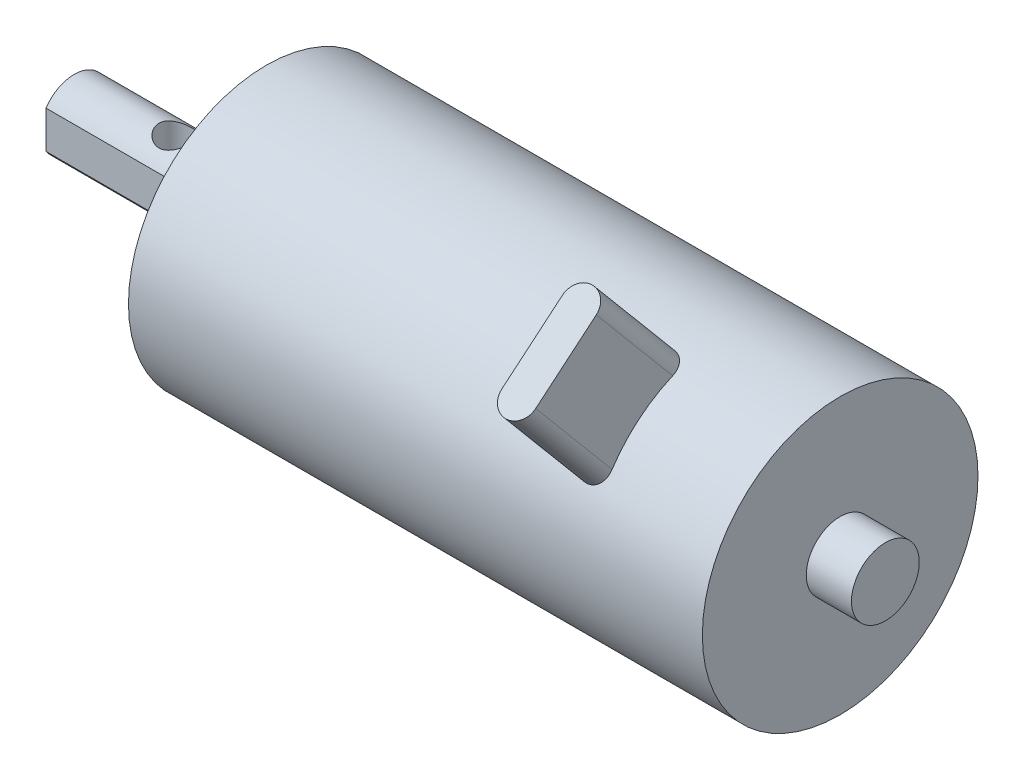
SolidWorks part; units mm, degrees
ref_plane "前视基准面" through (0, 0, 0) normal (0, 0, 1) x (1, 0, 0)
ref_plane "上视基准面" through (0, 0, 0) normal (0, 1, 0) x (1, 0, 0)
ref_plane "右视基准面" through (0, 0, 0) normal (1, 0, 0) x (0, 0, -1)
sketch "草图1" plane through (0, 0, 0) normal (0, 0, 1) x (1, 0, 0)
  line L0 (-36.1519, 0) -> (37.0633, 0) construction
  line L1 (-34.2314, 0) -> (-34.2314, 3)
  line L2 (-34.2314, 3) -> (-19.8314, 3)
  line L3 (-19.8314, 3) -> (-19.8314, 6.5)
  line L4 (-19.8314, 6.5) -> (-17.2314, 6.5)
  line L5 (-17.2314, 6.5) -> (-17.2314, 12.2)
  line L6 (-17.2314, 12.2) -> (33.5686, 12.2)
  line L7 (33.5686, 12.2) -> (33.5686, 3)
  line L8 (33.5686, 3) -> (37.5686, 3)
  line L9 (37.5686, 3) -> (37.5686, 0)
  line L10 (-34.2314, 0) -> (37.5686, 0)
  dimension "D1" = 6
  dimension "D2" = 17
  dimension "D3" = 2.6
  dimension "D4" = 50.8
  dimension "D5" = 71.8
  dimension "D6" = 3
  dimension "D7" = 12.2
  dimension "D8" = 13
revolve "旋转1" add sketch "草图1" angle 360 about L0
sketch "草图2" plane through (-17.2314, 0, 0) normal (-1, 0, 0) x (0, 0, 1)
  line L0 (-12.2, 0) -> (12.2, 0) construction
  line L1 (0, 12.2) -> (0, -12.2) construction
  line L2 (0, 0) -> (10.5655, -6.1) construction
  line L3 (0, 0) -> (-10.5655, -6.1) construction
  circle A0 centre (0, 0) radius 9.5 construction
  circle A1 centre (0, 0) radius 12.2 construction
  dimension "D1" = 19
  dimension "D2" = 30
  dimension "D3" = 30
hole_wizard "M3 螺纹孔1" positions "3D草图1" profile "草图3" tap size "M3" standard "GB"
sketch3d "3D草图1"
  line L0 (-17.2314, 12.2, 0) -> (-17.2314, -12.2, 0) construction
  line L1 (-17.2314, 0, 0) -> (-17.2314, -6.1, -10.5655) construction
  line L2 (-17.2314, 0, 0) -> (-17.2314, -6.1, 10.5655) construction
  circle A0 centre (-17.2314, 0, 0) radius 9.5 construction
  point P0 (-17.2314, 9.5, 0)
  point P6 (-26.7314, 0, 0)
  point P7 (-17.2314, -4.75, -8.2272)
  point P11 (-17.2314, -4.75, 8.2272)
sketch "草图3" plane through (-17.2314, 9.5, 0) normal (0, 1, 0) x (0, 0, 1)
  line L0 (0, 0) -> (0, 4.7511)
  line L1 (0, 4.7511) -> (1.25, 4)
  line L2 (1.25, 4) -> (1.25, 0)
  line L5 (1.25, 0) -> (0, 0)
  line L10 (0, 4.7511) -> (-1.25, 4) construction
  line L11 (0, -6.35) -> (0, 107.95) construction
  dimension "螺纹孔钻头直径" = 2.5
  dimension "螺纹孔钻头深度" = 4
  dimension "导头角度" = 118
cosmetic thread "孔螺蚊线1" parameters "D1"=4, "D2"=3
cosmetic thread "孔螺蚊线2" parameters "D1"=4, "D2"=3
cosmetic thread "孔螺蚊线3" parameters "D1"=4, "D2"=3
sketch "草图4" plane through (0, 0, 0) normal (0, 1, 0) x (1, 0, 0)
  line L0 (-34.2314, 3) -> (-34.2314, -3) construction
  circle A0 centre (-25.2314, 0) radius 1.5
  dimension "D1" = 3
  dimension "D2" = 9
extrude "切除-拉伸1" cut sketch "草图4" against normal blind 10 and the other way blind 10
sketch "草图5" plane through (-34.2314, 0, 0) normal (-1, 0, 0) x (0, 0, 1)
  line L0 (-12.2, 0) -> (12.2, 0) construction
  line L1 (2.5, 7.2601) -> (8.7917, 7.2601)
  line L2 (2.5, 7.2601) -> (2.5, -7.2601)
  line L3 (2.5, -7.2601) -> (8.7917, -7.2601)
  line L4 (8.7917, 7.2601) -> (8.7917, -7.2601)
  line L5 (2.5, 7.2601) -> (8.7917, -7.2601) construction
  line L6 (2.5, -7.2601) -> (8.7917, 7.2601) construction
  line L7 (0, 12.2) -> (0, -12.2) construction
  point P0 (5.6459, 0)
  dimension "D1" = 2.5
extrude "切除-拉伸2" cut sketch "草图5" against normal blind 11.5
hole_wizard "M3 螺纹孔2" positions "草图7" profile "草图6" tap size "M3" standard "GB"
sketch "草图7" plane through (-34.2314, 0, 0) normal (-1, 0, 0) x (0, 0, 1)
  point P0 (0, 0)
sketch "草图6" plane through (-34.2314, 0, 0) normal (0, 1, 0) x (0, 0, 1)
  line L0 (0, 0) -> (0, 6.2511)
  line L1 (0, 6.2511) -> (1.25, 5.5)
  line L2 (1.25, 5.5) -> (1.25, 0)
  line L5 (1.25, 0) -> (0, 0)
  line L10 (0, 6.2511) -> (-1.25, 5.5) construction
  line L11 (0, -6.35) -> (0, 107.95) construction
  dimension "螺纹孔钻头直径" = 2.5
  dimension "螺纹孔钻头深度" = 5.5
  dimension "导头角度" = 118
cosmetic thread "孔螺蚊线4" parameters "D1"=4, "D2"=3
ref_axis "基准轴1" through (33.5686, 0, 0) along (-1, 0, 0)
ref_plane "基准面2" through (0, 0, 0) normal (0, -0.766, -0.6428) x (-1, 0, 0)
ref_plane "基准面3" through (0, 9.3457, 7.842) normal (0, 0.766, 0.6428) x (1, 0, 0)
sketch "草图9" plane through (0, 9.3457, 7.842) normal (0, 0.766, 0.6428) x (1, 0, 0)
  line L0 (33.5686, 0) -> (22.0686, 0)
  line L1 (33.5686, -12.2) -> (33.5686, 12.2) construction
  line L2 (33.5686, 0) -> (-17.2314, 0) construction
  line L4 (20.5686, 5) -> (23.5686, 5)
  line L5 (20.5686, 5) -> (20.5686, -5)
  line L6 (20.5686, -5) -> (23.5686, -5)
  line L7 (23.5686, 5) -> (23.5686, -5)
  line L8 (20.5686, 5) -> (23.5686, -5) construction
  line L9 (20.5686, -5) -> (23.5686, 5) construction
extrude "凸台-拉伸2" add sketch "草图9" along normal blind 10 and the other way blind 10 contours L7 L4 L5 L6 region at (22.0686, 12.4926, 4.0918)
fillet "圆角2" radius 1.5 4 edges at (23.5686, 9.5516, 14.5417) (20.5686, 9.5516, 14.5417) (23.5686, 15.9794, 6.8813) (20.5686, 15.9794, 6.8813)
